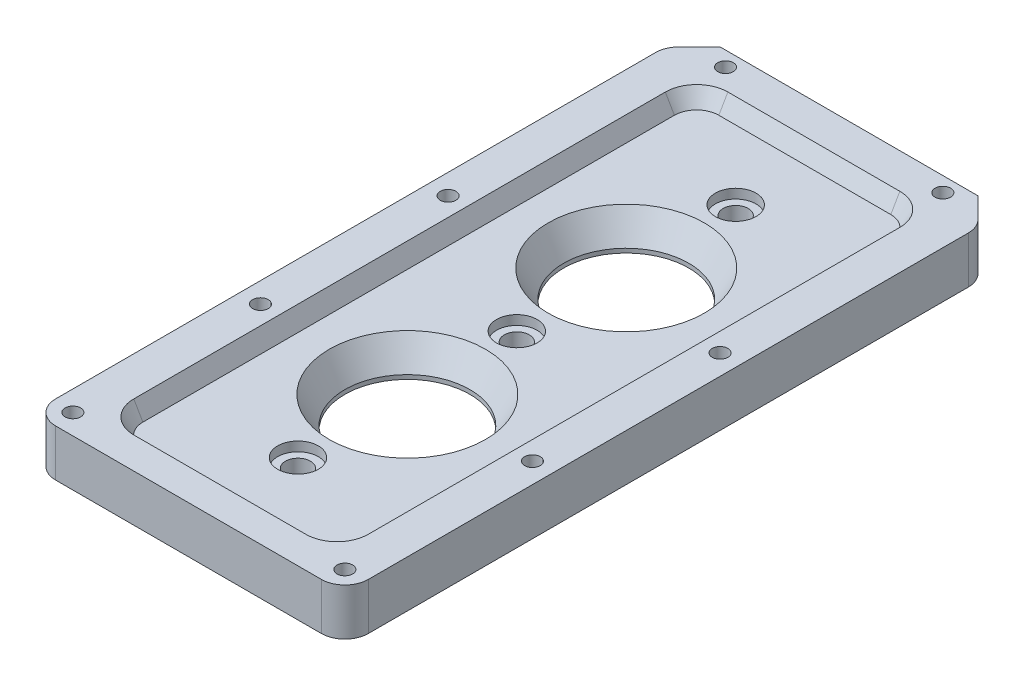
SolidWorks part; units mm, degrees
ref_plane "Front Plane" through (0, 0, 0) normal (0, 0, 1) x (1, 0, 0)
ref_plane "Top Plane" through (0, 0, 0) normal (0, 1, 0) x (1, 0, 0)
ref_plane "Right Plane" through (0, 0, 0) normal (1, 0, 0) x (0, 0, -1)
sketch "Sketch1" plane through (0, 0, 0) normal (0, 1, 0) x (1, 0, 0)
  line L2 (-42.5743, 39.6947) -> (-42.5743, -162.8053)
  line L3 (-42.5743, -162.8053) -> (57.4257, -162.8053)
  line L4 (57.4257, 39.6947) -> (57.4257, -162.8053)
  line L14 (-25.0743, 57.1947) -> (39.9257, 57.1947)
  line L17 (-25.0743, 57.1947) -> (39.9257, 57.1947)
  line L19 (-25.0743, 57.1947) -> (-42.5743, 39.6947)
  line L20 (39.9257, 57.1947) -> (57.4257, 39.6947)
  circle A1 centre (7.4257, 12.1947) radius 4
  circle A2 centre (7.4257, -57.8053) radius 4
  circle A3 centre (7.4257, -127.8053) radius 4
  circle A4 centre (-36.0743, -156.3053) radius 2.5
  circle A5 centre (50.9257, -156.3053) radius 2.5
  circle A6 centre (-36.0743, -96.3053) radius 2.5
  circle A7 centre (50.9257, -96.3053) radius 2.5
  circle A8 centre (-36.0743, -36.3053) radius 2.5
  circle A9 centre (50.9257, -36.3053) radius 2.5
  circle A10 centre (-27.3243, 43.6947) radius 2.5
  circle A11 centre (42.1757, 43.6947) radius 2.5
  circle A12 centre (7.4257, -22.8053) radius 20
  circle A13 centre (7.4257, -92.8053) radius 20
  point P15 (7.4257, -156.3053)
  point P32 (7.4257, 43.6947)
  point P39 (7.4257, 57.1947)
  dimension "D5" = 8
  dimension "D6" = 8
  dimension "D7" = 8
  dimension "D9" = 5
  dimension "D10" = 5
  dimension "D14" = 5
  dimension "D15" = 5
  dimension "D16" = 40
  dimension "D2" = 202.5
  dimension "D3" = 60
  dimension "D4" = 70
  dimension "D8" = 87
  dimension "D11" = 60
  dimension "D12" = 17.5
  dimension "D13" = 69.5
  dimension "D17" = 65
extrude "Boss-Extrude1" add sketch "Sketch1" along normal blind 15 contours L20 L14 L19 L2 L3 L4 A11 A10 A9 A8 A7 A6 A5 A4 A3 A2 A1 region at (7.4257, 0, 53.7191)
sketch "Sketch2" plane through (0, 15, 0) normal (0, 1, 0) x (1, 0, 0)
  circle A1 centre (7.4257, 12.1947) radius 6.5
  circle A2 centre (7.4257, -57.8053) radius 6.5
  circle A3 centre (7.4257, -127.8053) radius 6.5
  dimension "D1" = 13
  dimension "D2" = 13
  dimension "D3" = 13
extrude "Cut-Extrude1" cut sketch "Sketch2" against normal blind 8
fillet "Fillet1" radius 7.5 6 edges at (57.4257, 7.5, 162.8053) (-42.5743, 7.5, 162.8053) (-42.5743, 7.5, -39.6947) (-25.0743, 7.5, -57.1947) (57.4257, 7.5, -39.6947) (39.9257, 7.5, -57.1947)
sketch "Sketch4" plane through (0, 15, 0) normal (0, 1, 0) x (1, 0, 0)
  line L1 (-20.0743, -147.8053) -> (34.9257, -147.8053)
  line L2 (-25.0743, -142.8053) -> (-25.0743, 27.1947)
  line L3 (-20.0743, 32.1947) -> (34.9257, 32.1947)
  line L4 (39.9257, -142.8053) -> (39.9257, 27.1947)
  line L5 (-25.0743, -147.8053) -> (39.9257, 32.1947) construction
  line L6 (-25.0743, 32.1947) -> (39.9257, -147.8053) construction
  arc A0 (34.9257, -147.8053) -> (39.9257, -142.8053) centre (34.9257, -142.8053) ccw
  arc A1 (-20.0743, -147.8053) -> (-25.0743, -142.8053) centre (-20.0743, -142.8053) cw
  arc A2 (34.9257, 32.1947) -> (39.9257, 27.1947) centre (34.9257, 27.1947) cw
  arc A3 (-25.0743, 27.1947) -> (-20.0743, 32.1947) centre (-20.0743, 27.1947) cw
  point P0 (7.4257, -57.8053)
  dimension "D3" = 5
  dimension "D1" = 180
  dimension "D2" = 65
extrude "Cut-Extrude2" cut sketch "Sketch4" against normal blind 5
chamfer "Chamfer1" distance 5 angle 60 10 edges at (39.9257, 15, 57.8053) (38.4613, 15, -30.7303) (38.4613, 15, 146.3408) (7.4257, 15, -32.1947) (7.4257, 15, 147.8053) (-23.6098, 15, -30.7303) (-23.6098, 15, 146.3408) (-25.0743, 15, 57.8053) (7.4257, 10, 112.8053) (7.4257, 10, 42.8053) first distance on face at (7.4257, 15, 57.8053) first distance on face at (7.4257, 10, 42.8053)
sketch "Sketch5" plane through (0, 15, 0) normal (0, 1, 0) x (1, 0, 0)
  line L0 (-21.9677, 57.1947) -> (36.8191, 57.1947) construction
  line L1 (-33.8243, 65.9447) -> (48.6757, 65.9447)
  line L2 (-33.8243, 65.9447) -> (-33.8243, 48.4447)
  line L3 (-33.8243, 48.4447) -> (48.6757, 48.4447)
  line L4 (48.6757, 65.9447) -> (48.6757, 48.4447)
  line L5 (-33.8243, 65.9447) -> (48.6757, 48.4447) construction
  line L6 (-33.8243, 48.4447) -> (48.6757, 65.9447) construction
  line L7 (42.1224, 54.998) -> (55.229, 41.8914) construction
  point P0 (7.4257, 57.1947)
extrude "Cut-Extrude3" cut sketch "Sketch5" against normal up to surface (15 mm away) up to face at (7.4257, 0, 112.8053)
